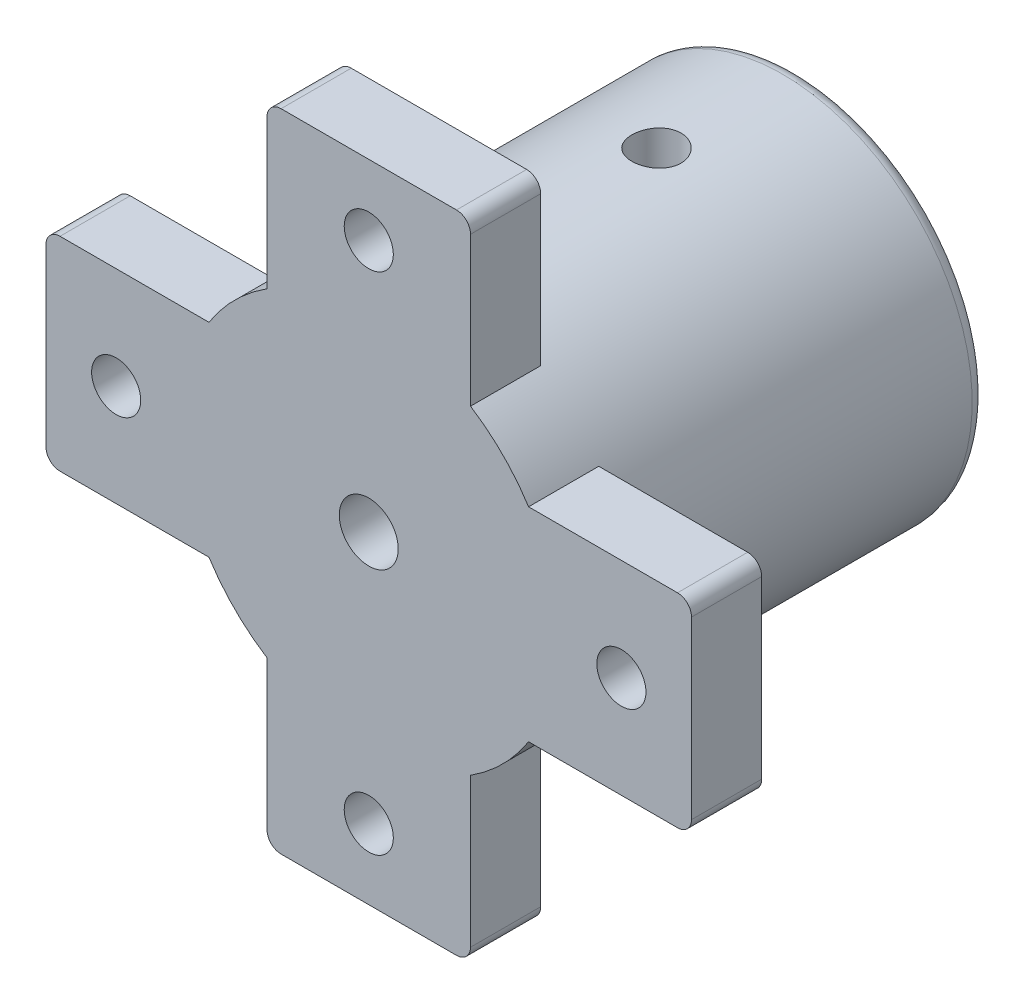
SolidWorks part; units mm, degrees
ref_plane "Front Plane" through (0, 0, 0) normal (0, 0, 1) x (1, 0, 0)
ref_plane "Top Plane" through (0, 0, 0) normal (0, 1, 0) x (1, 0, 0)
ref_plane "Right Plane" through (0, 0, 0) normal (1, 0, 0) x (0, 0, -1)
sketch "Sketch1" plane through (0, 0, 0) normal (0, 0, 1) x (1, 0, 0)
  circle A0 centre (0, 0) radius 2.1
  circle A1 centre (0, 0) radius 13.5
  dimension "D1" = 4.2
  dimension "D2" = 27
extrude "Boss-Extrude1" add sketch "Sketch1" along normal blind 5.5
sketch "Sketch2" plane through (0, 0, 5.5) normal (0, 0, 1) x (1, 0, 0)
  circle A2 centre (0, 0) radius 13.5
  circle A3 centre (0, 0) radius 2.1
  dimension "D1" = 4.2
  dimension "D2" = 27
extrude "Boss-Extrude2" add sketch "Sketch2" along normal blind 5
sketch "Sketch4" plane through (0, 0, 10.5) normal (0, 0, 1) x (1, 0, 0)
  line L17 (-7.25, 23) -> (7.25, 23)
  line L18 (-7.25, 23) -> (-7.25, 8)
  line L19 (-7.25, 8) -> (7.25, 8)
  line L20 (7.25, 23) -> (7.25, 8)
  line L21 (-7.25, 23) -> (7.25, 8) construction
  line L22 (-7.25, 8) -> (7.25, 23) construction
  line L23 (8, 7.25) -> (23, 7.25)
  line L24 (8, 7.25) -> (8, -7.25)
  line L25 (8, -7.25) -> (23, -7.25)
  line L26 (23, 7.25) -> (23, -7.25)
  line L27 (8, 7.25) -> (23, -7.25) construction
  line L28 (8, -7.25) -> (23, 7.25) construction
  line L29 (-23, 7.25) -> (-8, 7.25)
  line L30 (-23, 7.25) -> (-23, -7.25)
  line L31 (-23, -7.25) -> (-8, -7.25)
  line L32 (-8, 7.25) -> (-8, -7.25)
  line L33 (-23, 7.25) -> (-8, -7.25) construction
  line L34 (-23, -7.25) -> (-8, 7.25) construction
  line L35 (-7.25, -8) -> (7.25, -8)
  line L36 (-7.25, -8) -> (-7.25, -23)
  line L37 (-7.25, -23) -> (7.25, -23)
  line L38 (7.25, -8) -> (7.25, -23)
  line L39 (-7.25, -8) -> (7.25, -23) construction
  line L40 (-7.25, -23) -> (7.25, -8) construction
  point P0 (0, 15.5)
  point P6 (15.5, 0)
  point P11 (-15.5, 0)
  point P16 (0, -15.5)
  dimension "D1" = 14.5
  dimension "D2" = 15
  dimension "D3" = 8
  dimension "D4" = 8
  dimension "D5" = 8
  dimension "D6" = 8
extrude "Boss-Extrude4" add sketch "Sketch4" against normal blind 5
sketch "Sketch5" plane through (0, 0, 5.5) normal (0, 0, -1) x (-1, 0, 0)
  circle A0 centre (18, 0) radius 1.75
  circle A1 centre (-18, 0) radius 1.75
  circle A2 centre (0, 18) radius 1.75
  circle A3 centre (0, -18) radius 1.75
  dimension "D1" = 3.5
  dimension "D2" = 18
  dimension "D3" = 18
  dimension "D4" = 18
  dimension "D5" = 18
extrude "Cut-Extrude1" cut sketch "Sketch5" against normal up to next
sketch "Sketch6" plane through (0, 0, 0) normal (0, 0, -1) x (-1, 0, 0)
  line L5 (-5.3, 7.8) -> (5.3, 7.8)
  line L6 (-7.8, 5.3) -> (-7.8, -5.3)
  line L7 (-5.3, -7.8) -> (5.3, -7.8)
  line L8 (7.8, 5.3) -> (7.8, -5.3)
  line L9 (-7.8, 7.8) -> (7.8, -7.8) construction
  line L10 (-7.8, -7.8) -> (7.8, 7.8) construction
  circle A1 centre (0, 0) radius 13.5
  arc A3 (-7.8, -5.3) -> (-5.3, -7.8) centre (-5.3, -5.3) ccw
  arc A4 (5.3, 7.8) -> (7.8, 5.3) centre (5.3, 5.3) cw
  arc A5 (5.3, -7.8) -> (7.8, -5.3) centre (5.3, -5.3) ccw
  arc A6 (-5.3, 7.8) -> (-7.8, 5.3) centre (-5.3, 5.3) ccw
  dimension "D3" = 27
  dimension "D4" = 2.5
  dimension "D1" = 15.6
  dimension "D2" = 15.6
extrude "Boss-Extrude5" add sketch "Sketch6" along normal blind 20
sketch "Sketch7" plane through (0, 0, 0) normal (0, 1, 0) x (1, 0, 0)
  line L0 (13.5, 20) -> (-13.5, 20) construction
  circle A0 centre (0, 10) radius 1.75
  dimension "D2" = 3.5
  dimension "D1" = 10
extrude "Cut-Extrude2" cut sketch "Sketch7" against normal through all both and the other way through all
fillet "Fillet5" radius 1 9 edges at (7.0678, 7.0678, -20) (0, 7.8, -20) (-7.0678, 7.0678, -20) (-7.8, 0, -20) (-7.0678, -7.0678, -20) (0, -7.8, -20) (7.0678, -7.0678, -20) (7.8, 0, -20) (-13.5, 0, -20)
fillet "Fillet6" radius 1 8 edges at (-23, 7.25, 8) (-23, -7.25, 8) (-7.25, -23, 8) (7.25, -23, 8) (23, -7.25, 8) (-7.25, 23, 8) (7.25, 23, 8) (23, 7.25, 8)
